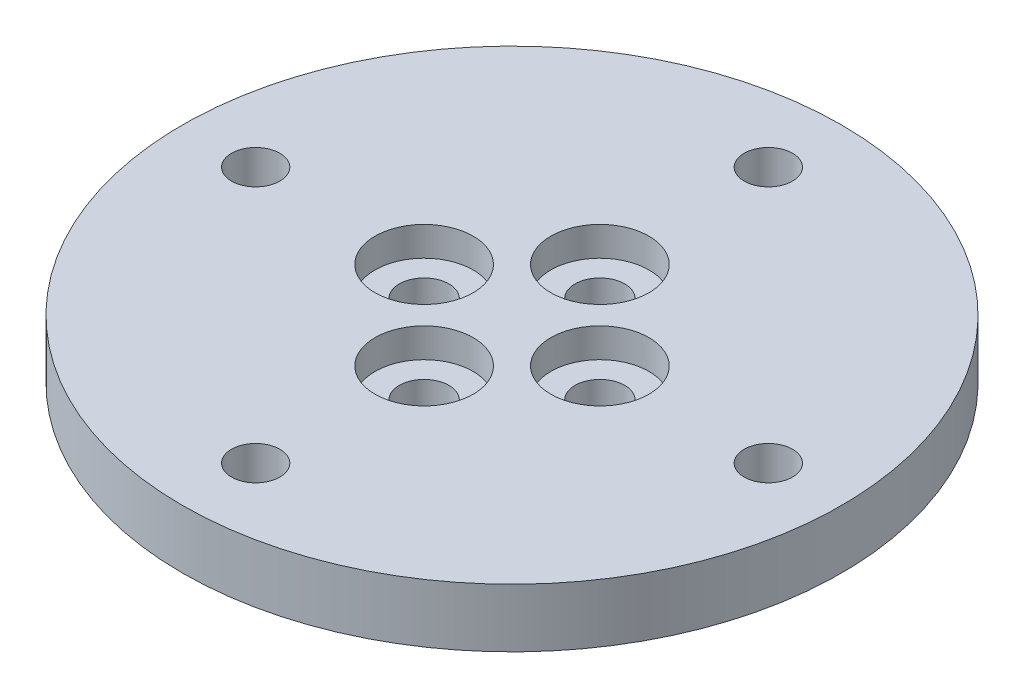
SolidWorks part; units mm, degrees
material "Сплав 2024"
ref_plane "Спереди" through (0, 0, 0) normal (0, 0, 1) x (1, 0, 0)
ref_plane "Сверху" through (0, 0, 0) normal (0, 1, 0) x (1, 0, 0)
ref_plane "Справа" through (0, 0, 0) normal (1, 0, 0) x (0, 0, -1)
sketch "Эскиз1" plane through (0, 0, 0) normal (0, 1, 0) x (1, 0, 0)
  line L0 (0, 22.5) -> (0, -22.5) construction
  line L1 (22.5, 0) -> (-22.5, 0) construction
  circle A0 centre (0, 0) radius 22.5
  dimension "D1" = 45
extrude "Бобышка-Вытянуть1" add sketch "Эскиз1" along normal blind 4
sketch "Эскиз2" plane through (0, 4, 0) normal (0, 1, 0) x (1, 0, 0)
  circle A0 centre (0, 0) radius 6 construction
  circle A1 centre (0, 0) radius 17.5 construction
  dimension "D1" = 12
  dimension "D2" = 35
hole_wizard "Цековка для  винта с полукруглой головкой M31" positions "Эскиз4" profile "Эскиз5" counterbore size "M3" standard "Ansi Metric" end condition through all
sketch "Эскиз4" plane through (0, 4, 0) normal (0, 1, 0) x (1, 0, 0)
  line L0 (0, 22.5) -> (0, -22.5) construction
  line L1 (22.5, 0) -> (-22.5, 0) construction
  circle A0 centre (0, 0) radius 6 construction
  point P0 (0, 6)
  point P6 (-6, 0)
  point P10 (0, -6)
  point P12 (6, 0)
sketch "Эскиз5" plane through (0, 4, -6) normal (1, 0, 0) x (0, 0, 1)
  line L0 (0, 0) -> (0, 4)
  line L1 (0, 4) -> (1.7, 4)
  line L3 (1.7, 4) -> (1.7, 2)
  line L4 (1.7, 2) -> (3.35, 2)
  line L5 (3.35, 2) -> (3.35, 0)
  line L7 (3.35, 0) -> (0, 0)
  line L11 (0, -6.35) -> (0, 107.95) construction
  dimension "Диаметр сквозного отверстия" = 3.4
  dimension "Глубина сквозного отверстия" = 4
  dimension "Диаметр цековки" = 6.7
  dimension "Глубина цековки" = 2
hole_wizard "Отверстие обработанное метчиком M4x0.71" positions "Эскиз7" profile "Эскиз6" tap size "M4x0.7" standard "Ansi Metric" end condition through all
sketch "Эскиз7" plane through (0, 4, 0) normal (0, 1, 0) x (1, 0, 0)
  line L0 (22.5, 0) -> (-22.5, 0) construction
  line L1 (0, 22.5) -> (0, -22.5) construction
  circle A0 centre (0, 0) radius 17.5 construction
  point P0 (-17.5, 0)
  point P6 (0, -17.5)
  point P10 (17.5, 0)
  point P12 (0, 17.5)
sketch "Эскиз6" plane through (-17.5, 4, 0) normal (1, 0, 0) x (0, 0, 1)
  line L0 (0, 0) -> (0, 4)
  line L1 (0, 4) -> (1.65, 4)
  line L2 (1.65, 4) -> (1.65, 0)
  line L5 (1.65, 0) -> (0, 0)
  line L11 (0, -6.35) -> (0, 107.95) construction
  dimension "Диаметр проходного сверла" = 3.3
  dimension "Глубина проходного сверла" = 4
cosmetic thread "Отверстие резьбы1" parameters "D2"=4
cosmetic thread "Отверстие резьбы2" parameters "D2"=4
cosmetic thread "Отверстие резьбы3" parameters "D2"=4
cosmetic thread "Отверстие резьбы4" parameters "D2"=4
